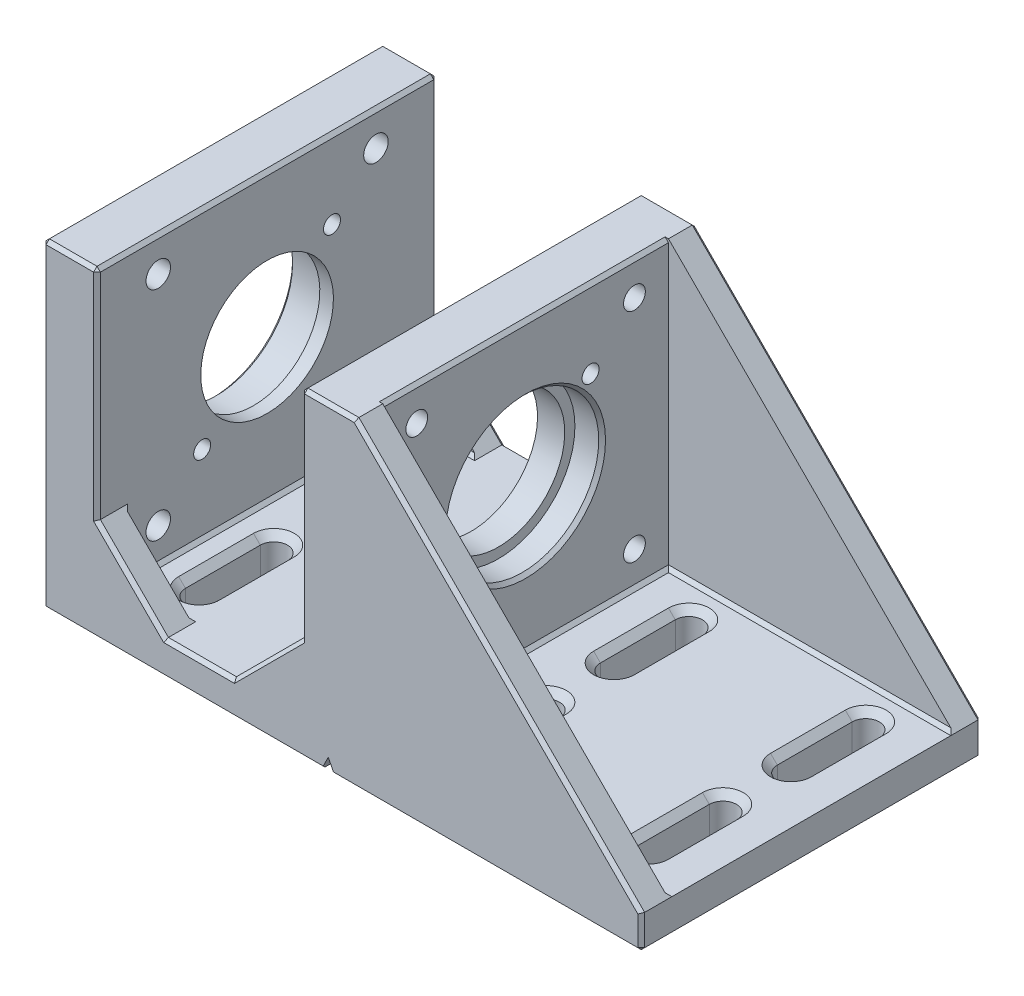
SolidWorks part; units mm, degrees
ref_plane "Front Plane" through (0, 0, 0) normal (0, 0, 1) x (1, 0, 0)
ref_plane "Top Plane" through (0, 0, 0) normal (0, 1, 0) x (1, 0, 0)
ref_plane "Right Plane" through (0, 0, 0) normal (1, 0, 0) x (0, 0, -1)
sketch "Sketch1" plane through (0, 0, 0) normal (0, 0, 1) x (1, 0, 0)
  line L0 (-8, 21) -> (-8, -11)
  line L1 (-18, -21) -> (-28, -21)
  line L2 (-38, -11) -> (-38, 21)
  line L3 (-38, 21) -> (-46, 21)
  line L4 (-46, 21) -> (-46, -26)
  line L5 (-46, -26) -> (42, -26)
  line L6 (42, -26) -> (42, -21)
  line L8 (42, -21) -> (0, 21)
  line L9 (0, 21) -> (-8, 21)
  line L10 (-28, -21) -> (-38, -11)
  line L11 (-8, -11) -> (-18, -21)
  point P1 (-8, -21)
  point P3 (-38, -21)
  dimension "D1" = 42
  dimension "D2" = 30
  dimension "D3" = 5
  dimension "D4" = 8
  dimension "D5" = 8
  dimension "D6" = 45
  dimension "D7" = 21
extrude "Boss-Extrude1" add sketch "Sketch1" along normal mid plane 50
sketch "Sketch2" plane through (0, 0, 0) normal (0, 0, 1) x (1, 0, 0)
  line L0 (-38, 21) -> (-38, -21)
  line L1 (-38, -21) -> (-8, -21)
  line L2 (-8, -21) -> (-8, 21)
  line L3 (-18, -21) -> (-28, -21) construction
  line L4 (-8, 21) -> (-38, 21)
  line L5 (0, 21) -> (0, -21)
  line L6 (0, -21) -> (42, -21)
  line L7 (42, -21) -> (0, 21)
extrude "Cut-Extrude1" cut sketch "Sketch2" along normal offset from surface 4 and the other way offset from surface 4 up to face at (-13.2727, -4.8182, 25) other way up to face at (-13.2727, -4.8182, -25)
sketch "Sketch3" plane through (0, 0, 0) normal (1, 0, 0) x (0, 0, -1)
  circle A0 centre (0, 0) radius 11.25
  dimension "D1" = 22.5
extrude "Cut-Extrude2" cut sketch "Sketch3" against normal through all both and the other way through all
sketch "Sketch4" plane through (-38, 0, 0) normal (-1, 0, 0) x (0, 0, 1)
  circle A1 centre (0, 0) radius 11.25 construction
  circle A2 centre (0, 0) radius 9.75
  circle A3 centre (0, 0) radius 9.75
  circle A4 centre (0, 0) radius 11.25
  dimension "D1" = 1.5
extrude "Boss-Extrude2" add sketch "Sketch4" along normal blind 2
hole_wizard "Tap Drill for M3x0.5 Tap1" positions "Sketch8" profile "Sketch10" hole size "M3x0.5" standard "ANSI Metric" end condition through all
sketch "Sketch8" plane through (-46, 0, 0) normal (-1, 0, 0) x (0, 0, 1)
  line L0 (-9.5459, 9.5459) -> (9.5459, -9.5459)
  line L2 (25, 21) -> (-25, 21) construction
  point P0 (-9.5459, 9.5459)
  point P2 (9.5459, -9.5459)
  point P11 (0, 0)
  dimension "D1" = 45
  dimension "D2" = 27
sketch "Sketch10" plane through (-46, 9.5459, -9.5459) normal (0, 1, 0) x (0, 0, 1)
  line L0 (0, 0) -> (0, 88)
  line L1 (0, 88) -> (1.25, 88)
  line L2 (1.25, 88) -> (1.25, 0)
  line L5 (1.25, 0) -> (0, 0)
  line L11 (0, -6.35) -> (0, 107.95) construction
  dimension "Thru Hole Dia." = 2.5
  dimension "Thru Hole Depth" = 88
hole_wizard "CSK for M3 Flat Head Machine Screw1" positions "Sketch12" profile "Sketch13" countersink size "M3" standard "ANSI Metric" end condition up to next
sketch "Sketch12" plane through (-8, 0, 0) normal (-1, 0, 0) x (0, 0, 1)
  line L1 (16, -16) -> (-16, -16) construction
  line L2 (16, -16) -> (16, 16) construction
  line L3 (16, 16) -> (-16, 16) construction
  line L4 (-16, -16) -> (-16, 16) construction
  line L5 (16, -16) -> (-16, 16) construction
  line L6 (16, 16) -> (-16, -16) construction
  point P0 (-16, 16)
  point P2 (16, 16)
  point P4 (16, -16)
  point P6 (-16, -16)
  point P9 (0, 0)
  dimension "D1" = 32
sketch "Sketch13" plane through (-8, 16, -16) normal (0, 1, 0) x (0, 0, 1)
  line L0 (0, 0) -> (0, 8)
  line L1 (0, 8) -> (1.6, 8)
  line L2 (1.6, 8) -> (1.6, 1.55)
  line L3 (1.6, 1.55) -> (3.15, 0)
  line L5 (3.15, 0) -> (0, 0)
  line L6 (-1.6, 1.55) -> (-3.15, 0) construction
  line L11 (0, -6.35) -> (0, 107.95) construction
  dimension "Thru Hole Dia." = 3.2
  dimension "Thru Hole Depth" = 8
  dimension "Near C'Sink Dia." = 6.3
  dimension "Near C'Sink Angle" = 90
sketch "Sketch21" plane through (0, 0, 0) normal (0, 0, 1) x (1, 0, 0)
  line L0 (-5, -26) -> (-4, -24)
  line L1 (-46, -26) -> (42, -26) construction
  line L2 (-4, -24) -> (-3, -26)
  line L3 (-3, -26) -> (-5, -26)
  line L4 (0, 21) -> (-8, 21) construction
  point P4 (0, 0)
  point P8 (-4, 21)
  point P9 (-2.975, -26)
  dimension "D1" = 2
  dimension "D2" = 2
extrude "Cut-Extrude4" cut sketch "Sketch21" against normal through all both and the other way through all
chamfer "Chamfer1" distance 0.5 angle 45 45 edges at (0, 0, -11.25) (-46, 0, -11.25) (-8, -16, -21) (-8, -16, 21) (-13, -21, 21) (-8, -21, 0) (-13, -21, -21) (-38, -16, 21) (-38, -16, -21) (-33, -21, -21) (-38, -21, 0) (-33, -21, 21) (21, -21, 21) (0, -21, 0) (21, -21, -21) (0, 21, 0) (-8, 21, 0) (-4, 21, 25) (-8, 5, 25) (-13, -16, 25) (-23, -21, 25) (-33, -16, 25) (-38, 5, 25) (-42, 21, 25) (-38, 21, 0) (-46, 21, 0) (-42, 21, -25) (-38, 5, -25) (-33, -16, -25) (-23, -21, -25) (-13, -16, -25) (-8, 5, -25) (-4, 21, -25) (21, 0, 25) (21, 0, -25) (42, -23.5, 25) (42, -23.5, -25) (-46, -2.5, -25) (-46, -2.5, 25) (42, -26, 0) (-25.5, -26, -25) (19.5, -26, -25) (-46, -26, 0) (19.5, -26, 25) (-25.5, -26, 25)
extrude "Boss-Extrude3" add sketch "Sketch4<2>" against normal blind 4 from surface starting at face at (-8, -5.5, 0)
sketch "Sketch4<2>" plane through (-38, 0, 0) normal (-1, 0, 0) x (0, 0, 1) same geometry as "Sketch4"
hole_wizard "M3 Clearance Hole1" positions "Sketch18" profile "Sketch17" hole size "M3" standard "ANSI Metric" end condition up to next
sketch "Sketch18" plane through (-46, 0, 0) normal (-1, 0, 0) x (0, 0, 1)
  circle A0 centre (-16, -16) radius 1.6 construction
  circle A1 centre (16, -16) radius 1.6 construction
  circle A2 centre (16, 16) radius 1.6 construction
  circle A3 centre (-16, 16) radius 1.6 construction
  circle A4 centre (-16, -16) radius 1.6
  circle A5 centre (16, -16) radius 1.6
  circle A6 centre (16, 16) radius 1.6
  circle A7 centre (-16, 16) radius 1.6
  point P1 (-16, -16)
  point P3 (16, -16)
  point P5 (16, 16)
  point P7 (-16, 16)
sketch "Sketch17" plane through (-46, -16, -16) normal (0, 1, 0) x (0, 0, 1)
  line L0 (0, 0) -> (0, 8)
  line L1 (0, 8) -> (1.8, 8)
  line L2 (1.8, 8) -> (1.8, 0)
  line L5 (1.8, 0) -> (0, 0)
  line L11 (0, -6.35) -> (0, 107.95) construction
  dimension "Thru Hole Dia." = 3.6
  dimension "Thru Hole Depth" = 8
sketch "Sketch19" plane through (0, -21, 0) normal (0, 1, 0) x (1, 0, 0)
  line L0 (-32, 5) -> (-32, 16) construction
  line L1 (-34, 5) -> (-34, 16)
  line L2 (-30, 5) -> (-30, 16)
  line L3 (-14, 5) -> (-14, 16) construction
  line L4 (-16, 5) -> (-16, 16)
  line L5 (-12, 5) -> (-12, 16)
  line L6 (-17.5, 21) -> (-8.5, 21) construction
  line L7 (-38, -20.5) -> (-38, 20.5) construction
  line L8 (-8, -24.5) -> (-8, 24.5) construction
  line L9 (8, 5) -> (8, 16) construction
  line L10 (6, 5) -> (6, 16)
  line L11 (10, 5) -> (10, 16)
  line L12 (34, 5) -> (34, 16) construction
  line L13 (32, 5) -> (32, 16)
  line L14 (36, 5) -> (36, 16)
  line L16 (0, -21) -> (0, 21) construction
  line L17 (42, -20.5) -> (42, 20.5) construction
  arc A0 (-34, 5) -> (-30, 5) centre (-32, 5) ccw
  arc A1 (-30, 16) -> (-34, 16) centre (-32, 16) ccw
  arc A2 (-16, 5) -> (-12, 5) centre (-14, 5) ccw
  arc A3 (-12, 16) -> (-16, 16) centre (-14, 16) ccw
  arc A4 (6, 5) -> (10, 5) centre (8, 5) ccw
  arc A5 (10, 16) -> (6, 16) centre (8, 16) ccw
  arc A6 (32, 5) -> (36, 5) centre (34, 5) ccw
  arc A7 (36, 16) -> (32, 16) centre (34, 16) ccw
  point P2 (-32, 10.5)
  point P7 (-14, 10.5)
  point P21 (8, 10.5)
  point P28 (34, 10.5)
  dimension "D3" = 2
  dimension "D1" = 5
  dimension "D2" = 5
  dimension "D4" = 6
  dimension "D5" = 6
  dimension "D6" = 8
  dimension "D7" = 8
extrude "Cut-Extrude3" cut sketch "Sketch19" against normal through all
chamfer "Chamfer2" distance 1 angle 45 16 edges at (36, -21, -10.5) (34, -21, -18) (34, -21, -3) (32, -21, -10.5) (10, -21, -10.5) (8, -21, -18) (8, -21, -3) (6, -21, -10.5) (-12, -21, -10.5) (-14, -21, -18) (-14, -21, -3) (-16, -21, -10.5) (-34, -21, -10.5) (-32, -21, -3) (-32, -21, -18) (-30, -21, -10.5)
mirror "Mirror1" about plane through (0, 0, 0) normal (0, 0, 1) of "Chamfer2", "Cut-Extrude3"
